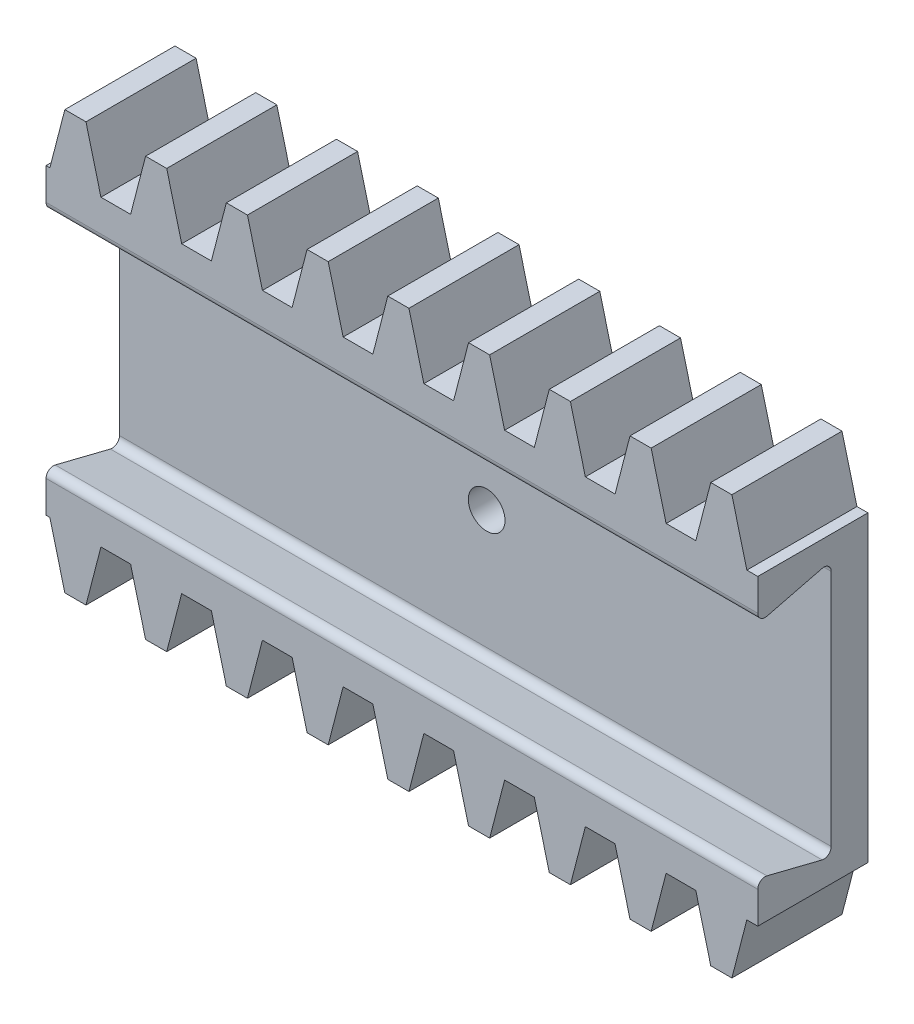
SolidWorks part; units mm, degrees
extrude "Blank" add sketch "BlankSke" against normal blind 3
sketch "BlankSke" plane through (0, 0, 0) normal (0, 0, 1) x (1, 0, 0)
  line L1 (0, 0) -> (25, 0)
  line L2 (0, 0) -> (0, 5.7)
  line L3 (0, 5.7) -> (25, 5.7)
  line L4 (25, 0) -> (25, 5.7)
  dimension "Length" = 25
ref_plane "Plane1" through (0, 0, 0) normal (0, 0, 1) x (1, 0, 0)
ref_plane "Plane2" through (0, 0, 0) normal (0, 1, 0) x (1, 0, 0)
ref_plane "Plane3" through (0, 0, 0) normal (1, 0, 0) x (0, 0, -1)
other "Configuration Table"
sketch "HoldingSke" plane through (0, 0, 0) normal (0, 1, 0) x (1, 0, 0)
  line L0 (0, 0) -> (0.1988, 1.4147)
  line L1 (-15, 0) -> (100, 0) construction
  line L2 (0, 0) -> (-2.1039, 2.3779)
  line L3 (0, 0) -> (-11.863, 4.5341)
  line L4 (0, 0) -> (8.4147, 1.9427)
  line L5 (0, 0) -> (-23.7986, -8.8762)
  line L6 (0, 0) -> (-10.5278, -7.1032)
  line L9 (-67.7845, 28.3722) -> (-43.5808, 34.6317)
  line L10 (-76.2, 3.0779) -> (-71.2, 3.0779)
  line L11 (0, 0) -> (-3, 0)
  line L12 (-76.2, 101.6) -> (-76.173, 101.6)
  line L13 (24.9733, 27.94) -> (52.9518, 28.4284)
  line L14 (24.9733, 27.94) -> (24.9743, 27.94)
  line L15 (24.9733, 27.94) -> (100.4006, 29.5858)
  circle A0 centre (0, 0) radius 19.05
  circle A1 centre (0, 0) radius 2.5
  circle A2 centre (0, 0) radius 12.7
  dimension "Num_teeth" = 13
  dimension "Width" = 3
  dimension "Length" = 25
  dimension "Pitch_height" = 5
sketch "TooCutSkeIll" plane through (0, 0, 0) normal (0, 0, 1) x (1, 0, 0)
  line L0 (-0.8064, 5.679) -> (-0.4386, 4.2569)
  line L1 (-0.2682, 4.125) -> (0.2682, 4.125)
  line L2 (0.4386, 4.2569) -> (0.8064, 5.679)
  line L3 (25, 5.7) -> (0, 5.7) construction
  line L4 (0, 0) -> (0, 64.897) construction
  line L5 (-13.208, 5) -> (12.954, 5) construction
  line L6 (0, 0) -> (25, 0) construction
  line L7 (0.6308, 5) -> (0.6308, 48.7463) construction
  line L8 (-0.6308, 5) -> (-0.6308, 48.7463) construction
  line L9 (0.8335, 5.7) -> (0.8335, 5.7254)
  line L10 (-0.8335, 5.7) -> (-0.8335, 5.7254)
  line L11 (-0.8335, 5.7254) -> (0.8335, 5.7254)
  arc A0 (0.2682, 4.125) -> (0.4386, 4.2569) centre (0.2682, 4.301) ccw
  arc A1 (-0.4386, 4.2569) -> (-0.2682, 4.125) centre (-0.2682, 4.301) ccw
  arc A2 (0.8335, 5.7) -> (0.8064, 5.679) centre (0.8335, 5.672) ccw
  arc A3 (-0.8064, 5.679) -> (-0.8335, 5.7) centre (-0.8335, 5.672) ccw
  dimension "Addendum_plus" = 0.7254
  dimension "Pitch_height" = 5
  dimension "Pressure_angle" = 14.5
  dimension "Gap_width" = 1.2616
  dimension "Dedendum" = 0.875
extrude "ToothCutIll" [suppressed] cut sketch "TooCutSkeIll" against normal through all
sketch "TooCutSkeSim" plane through (0, 0, 0) normal (0, 0, 1) x (1, 0, 0)
  line L0 (0.4045, 4.125) -> (-0.4045, 4.125)
  line L1 (0.8184, 5.7254) -> (0.4045, 4.125)
  line L2 (0, 17.4625) -> (0, 53.467) construction
  line L3 (0.8184, 5.7254) -> (-0.8184, 5.7254)
  line L6 (-0.8184, 5.7254) -> (-0.4045, 4.125)
  line L9 (-0.6308, 5) -> (0.6308, 5) construction
  line L10 (0, 0) -> (25, 0) construction
  line L11 (0.6308, 5) -> (0.6308, 53.467) construction
  line L12 (-0.6308, 5) -> (-0.6308, 53.467) construction
  dimension "Addendum_plus" = 0.7254
  dimension "Pitch_height" = 5
  dimension "Pressure_angle" = 14.5
  dimension "Gap_width" = 1.2616
  dimension "Dedendum" = 0.875
extrude "ToothCutSim" cut sketch "TooCutSkeSim" against normal through all
pattern_linear "TeethCuts" count 13 spacing 2.1991 along (1, 0, 0) of "ToothCutIll", "ToothCutSim"
mirror "镜向1" [suppressed]
mirror "镜向2" about plane through (0, 0, -3) normal (0, -1, 0) of "Blank", "ToothCutSim", "TeethCuts"
sketch "草图1" plane through (0, 0, 0) normal (-1, 0, 0) x (0, 0, 1)
  line L1 (0, 4.125) -> (0, -4.125) construction
  line L4 (-3, 0) -> (0, 0) construction
  line L5 (-3, 4.125) -> (-3, -4.125) construction
  line L7 (0, -3) -> (0, 3)
  line L8 (0, 3) -> (-2, 3.5)
  line L9 (-2, 3.5) -> (-2, -3.5)
  line L10 (0, -3) -> (-2, -3.5)
  point P11 (-2.5, 0)
  point P12 (-2, 0)
  dimension "D1" = 3
  dimension "D2" = 3.5
  dimension "D3" = 2
extrude "切除-拉伸2" cut sketch "草图1" against normal through all
fillet "圆角1" radius 0.2 1 edges at (12.5, -3.5, -2)
fillet "圆角2" radius 0.2 1 edges at (12.5, 3.5, -2)
fillet "圆角3" radius 0.2 2 edges at (12.5, -3, 0) (12.5, 3, 0)
sketch "草图2" plane through (0, 0, -3) normal (0, 0, -1) x (-1, 0, 0)
  line L0 (0, 0) -> (-25, 0) construction
  line L1 (0, 4.125) -> (0, -4.125) construction
  line L2 (-25, -5.692) -> (-25, 5.692) construction
  circle A0 centre (-12.5, 0) radius 2
  dimension "D1" = 4
extrude "凸台-拉伸1" add sketch "草图2" along normal blind 1.5
sketch "草图3" plane through (0, 0, -4.5) normal (0, 0, -1) x (-1, 0, 0)
  circle A0 centre (-12.5, 0) radius 0.5
  dimension "D1" = 1
extrude "切除-拉伸3" cut sketch "草图3" against normal through all
sketch "草图4" plane through (0, 0, -3) normal (0, 0, -1) x (-1, 0, 0)
  line L0 (-12.5, 0) -> (-21.8848, 0) construction
  line L1 (-12.5, 0) -> (-2.5, 0) construction
  line L2 (-21.8848, 2.1496) -> (-21.8848, -2.1496)
  line L3 (-22.3956, 4.125) -> (-22.803, 5.7) construction
  line L4 (-2.5, 4.125) -> (-2.5, -4.125)
  line L6 (-1.7946, -4.125) -> (-2.6036, -4.125) construction
  line L7 (-22.3956, -4.125) -> (-22.803, -5.7) construction
  line L9 (-1.7946, 4.125) -> (-2.6036, 4.125) construction
  line L10 (-21.8848, 2.1496) -> (-21.8848, 5.9598)
  line L11 (-21.8848, 5.9598) -> (-25.6774, 5.9598)
  line L12 (-25.6774, 5.9598) -> (-25.6774, -6.5792)
  line L13 (-25.6774, -6.5792) -> (-21.8848, -6.5792)
  line L14 (-21.8848, -6.5792) -> (-21.8848, -2.1496)
  line L15 (-2.5, 4.125) -> (-2.5, 6.4022)
  line L16 (-2.5, 6.4022) -> (0, 6.4022)
  line L17 (0, 6.4022) -> (0, -6.0736)
  line L18 (0, -6.0736) -> (-2.5, -6.0736)
  line L19 (-2.5, -6.0736) -> (-2.5, -4.125)
  dimension "D2" = 10
extrude "切除-拉伸4" cut sketch "草图4" against normal blind 10
equation "' \"Module@HoldingSke\" = 6.35"
equation "' \"Num_teeth@HoldingSke\" = 12"
equation "' \"Ap@HoldingSke\" =  20"
equation "' \"Ap@HoldingSke\" = 20"
equation "' \"Width@HoldingSke\" = 0.25 * 25.4"
equation "' \"Show_teeth@HoldingSke\" = 500"
equation "' \"Backlash@HoldingSke\" = 0.009 * 25.4"
equation "' \"Addendum_fac@HoldingSke\" = 1.0"
equation "' \"Dedendum_fac@HoldingSke\" = 1.25"
equation "' \"Dedendum_add@HoldingSke\" = 0.00005 * 25.4"
equation "' \"Clearance_fac@HoldingSke\" = 0.25"
equation "' \"Pitch_height@HoldingSke\" = 1 * 25.4"
equation "' \"Length@HoldingSke\" = 4.71 * 25.4"
equation "\"Pitch@HoldingSke\" = 1 / \"Module@HoldingSke\""
equation "\"MPH@HoldingSke\" = \"Dedendum_fac@HoldingSke\" / \"Pitch@HoldingSke\" + 2 * \"Dedendum_add@HoldingSke\" + 0.002 * 25.4"
equation "\"MPH@HoldingSke\" = ((sgn( \"MPH@HoldingSke\" - \"Pitch_height@HoldingSke\")+1)*( \"MPH@HoldingSke\" - \"Pitch_height@HoldingSke\"))/2 + \"Pitch_height@HoldingSke\""
equation "\"Blank_height@BlankSke\" = \"Pitch_height@HoldingSke\" + \"Addendum_fac@HoldingSke\"  / \"Pitch@HoldingSke\" "
equation "\"Length@BlankSke\" =  \"Length@HoldingSke\""
equation "\"Face_width@Blank\" = \"Width@HoldingSke\""
equation "\"Pressure_angle@TooCutSkeIll\" = \"Ap@HoldingSke\""
equation "\"Addendum_plus@TooCutSkeIll\" =  \"Addendum_fac@HoldingSke\"  / \"Pitch@HoldingSke\" + 0.001 *25.4"
equation "\"Dedendum@TooCutSkeIll\" = \"Dedendum_fac@HoldingSke\"  / \"Pitch@HoldingSke\""
equation "\"Pitch_height@TooCutSkeIll\" =  \"MPH@HoldingSke\""
equation "\"Gap_width@TooCutSkeIll\" = 3.14159265 / 2 / \"Pitch@HoldingSke\" + 6 * \"Backlash@HoldingSke\""
equation "\"Pressure_angle@TooCutSkeSim\" = \"Ap@HoldingSke\""
equation "\"Addendum_plus@TooCutSkeSim\" =  \"Addendum_fac@HoldingSke\"  / \"Pitch@HoldingSke\" + 0.001 * 25.4"
equation "\"Dedendum@TooCutSkeSim\" = \"Dedendum_fac@HoldingSke\"  / \"Pitch@HoldingSke\""
equation "\"Pitch_height@TooCutSkeSim\" =  \"MPH@HoldingSke\""
equation "\"Gap_width@TooCutSkeSim\" = 3.14159265 / 2 / \"Pitch@HoldingSke\" + 6 * \"Backlash@HoldingSke\""
equation "\"Root_fillet@TooCutSkeIll\" = \"Clearance_fac@HoldingSke\" / \"Pitch@HoldingSke\" + \"Dedendum_add@HoldingSke\""
equation "\"Break_rad@TooCutSkeIll\" = 0.02 / \"Pitch@HoldingSke\" * 2"
equation "\"Linear_pitch@TeethCuts\" = 3.14159265 / \"Pitch@HoldingSke\""
equation "\"Num_teeth@HoldingSke\" = int( ( \"Length@HoldingSke\" + 0 ) / (3.14159265 / \"Pitch@HoldingSke\")) + 0.9999  + 1"
equation " \"Num_teeth@TeethCuts\" = int( \"Show_teeth@HoldingSke\" ) + 1"
equation " \"Num_teeth@TeethCuts\" = ((sgn( \"Num_teeth@TeethCuts\" - \"Num_teeth@HoldingSke\" )-1)*( \"Num_teeth@TeethCuts\" - \"Num_teeth@HoldingSke\" ))/-2+ \"Num_teeth@HoldingSke\""
equation " \"Num_teeth@TeethCuts\" = ((sgn( \"Num_teeth@TeethCuts\" - 2.0)+1)*( \"Num_teeth@TeethCuts\" - 2.0))/2 +2.0"
